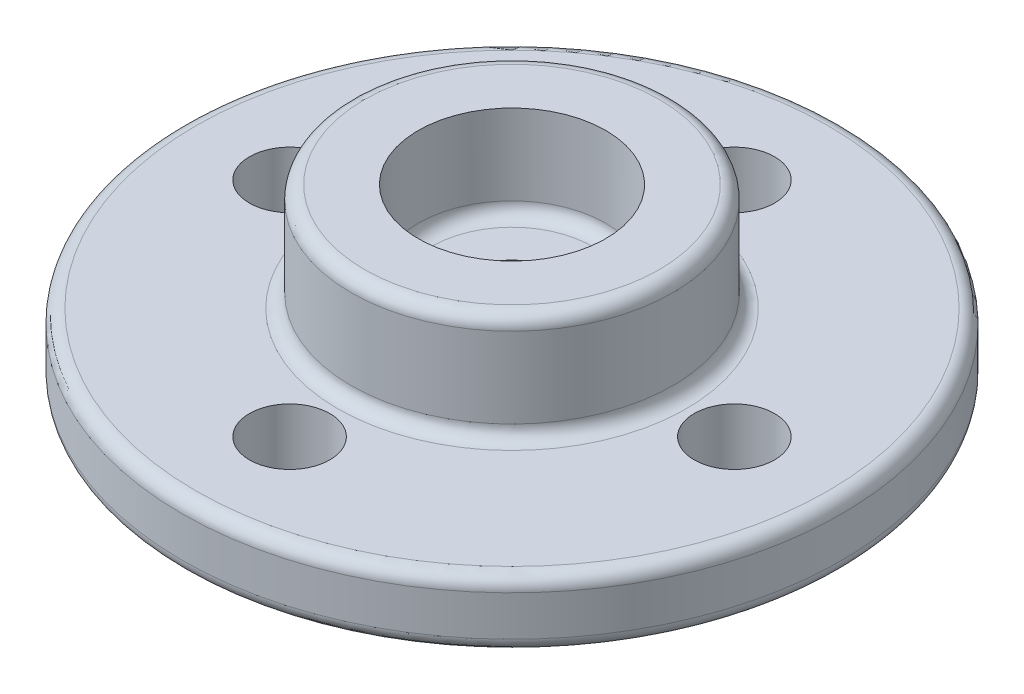
SolidWorks part; units mm, degrees
ref_plane "Front Plane" through (0, 0, 0) normal (0, 0, 1) x (1, 0, 0)
ref_plane "Top Plane" through (0, 0, 0) normal (0, 1, 0) x (1, 0, 0)
ref_plane "Right Plane" through (0, 0, 0) normal (1, 0, 0) x (0, 0, -1)
sketch "Sketch1" plane through (0, 0, 0) normal (1, 0, 0) x (0, 0, -1)
  line L0 (1.5, 0) -> (1.5, 3)
  line L2 (13.53, 0) -> (-13.53, 0) construction
  line L3 (1.5, 3) -> (3.5, 3)
  line L4 (3.5, 3) -> (3.5, 6.5)
  line L5 (3.5, 6.5) -> (6, 6.5)
  line L7 (6, 6.5) -> (6, 2.5)
  line L8 (6, 2.5) -> (12.3, 2.5)
  line L9 (12.3, 2.5) -> (12.3, 0)
  line L10 (12.3, 0) -> (1.5, 0)
  line L11 (0, -5.7365) -> (0, 32.5513) construction
  line L12 (0, 3.575) -> (0, -3.575) construction
  dimension "D1" = 3.5
  dimension "D2" = 1.5
  dimension "D3" = 12.3
  dimension "D4" = 6
  dimension "D5" = 2.5
  dimension "D6" = 4
  dimension "D7" = 3.5
revolve "Revolve1" add sketch "Sketch1" angle 360 about L11
sketch "Sketch2" plane through (0, 0, 0) normal (0, -1, 0) x (1, 0, 0)
  line L0 (0, -3.575) -> (0, 3.575) construction
  line L1 (3.575, 0) -> (-3.575, 0) construction
  circle A0 centre (0, -8.3) radius 1.5
  dimension "D1" = 3
  dimension "D2" = 8.3
extrude "Cut-Extrude1" cut sketch "Sketch2" against normal blind 10
pattern_circular "CirPattern1" count 4 over 360 about axis through (0, -5.7365, 0) along (0, -1, 0) of "Cut-Extrude1"
fillet "Fillet1" radius 0.5 5 edges at (0, 0, -12.3) (0, 2.5, -12.3) (0, 6.5, -6) (0, 3, -3.5) (0, 2.5, -6)
